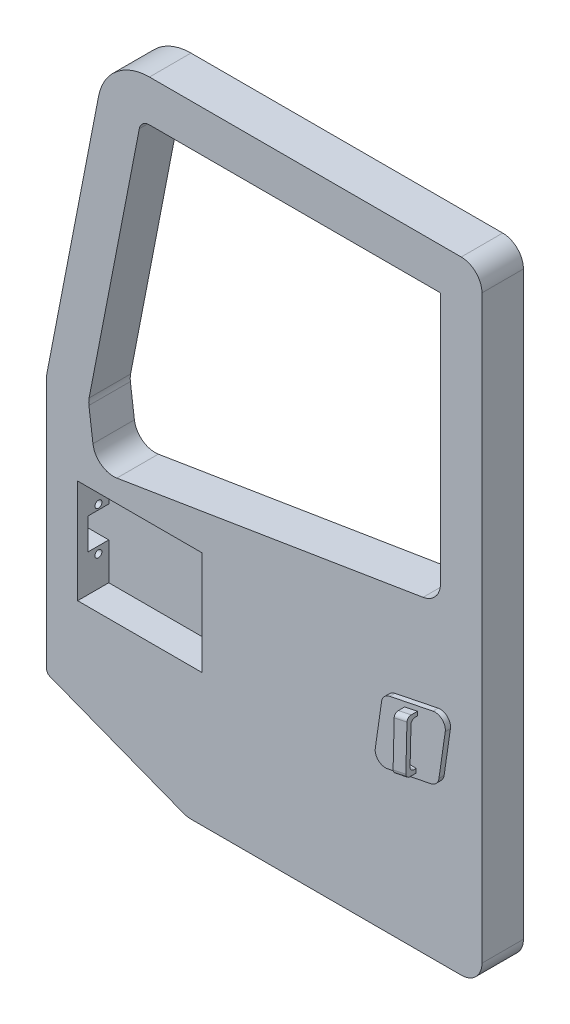
SolidWorks part; units mm, degrees
ref_plane "Front Plane" through (0, 0, 0) normal (0, 0, 1) x (1, 0, 0)
ref_plane "Top Plane" through (0, 0, 0) normal (0, 1, 0) x (1, 0, 0)
ref_plane "Right Plane" through (0, 0, 0) normal (1, 0, 0) x (0, 0, -1)
sketch "Sketch2" plane through (0, 0, 0) normal (0, 0, 1) x (1, 0, 0)
  line L0 (-405.8971, 659.2079) -> (-532.5433, 7.5919)
  line L1 (-179.7693, -762.022) -> (482.6, -762.022)
  line L3 (-281.2299, 761.978) -> (482.6, 761.978)
  line L4 (533.4, -711.222) -> (533.4, 711.178)
  line L5 (-459.8603, -656.939) -> (-452.0517, -645.784) construction
  line L6 (-417.9715, 597.0829) -> (44.1715, -63.1001) construction
  line L8 (-525.2852, -631.9868) -> (-198.1028, -758.5984)
  line L9 (-306.1633, 639.824) -> (-429.1581, 6.9955)
  line L10 (-429.6693, -9.2299) -> (-419.7789, -85.4932)
  line L14 (-281.2299, 660.378) -> (431.8, 660.378)
  line L15 (389.1621, -6.9365) -> (-361.2381, -129.0997)
  line L16 (431.7995, 43.2033) -> (431.8, 660.378)
  line L17 (431.8, -660.422) -> (431.8, 660.378) construction
  line L18 (-170.2829, -660.422) -> (431.8, -660.422) construction
  line L20 (-354.461, -589.1496) -> (-170.2829, -660.422) construction
  line L21 (-55.5325, -79.3316) -> (521.0599, 744.3665) construction
  line L22 (-306.1633, 639.824) -> (-430.7268, -1.0758) construction
  line L23 (-430.7268, -1.0758) -> (-354.461, -589.1496) construction
  line L24 (-416.9351, -673.9156) -> (-198.1028, -758.5984) construction
  line L25 (-179.7693, -762.022) -> (482.6, -762.022)
  line L27 (-281.2299, 761.978) -> (482.6, 761.978)
  line L28 (533.4, -711.222) -> (533.4, 711.178)
  line L29 (-459.8603, -656.939) -> (521.0599, 744.3665) construction
  line L30 (-417.9715, 597.0829) -> (521.0843, -744.3822) construction
  line L31 (-533.4018, 0.6529) -> (-448.7537, -652.0554) construction
  line L34 (-281.2299, 761.978) -> (482.6, 761.978)
  line L35 (-533.4018, 0.6529) -> (-533.4018, -620.1427)
  line L36 (-179.7693, -762.022) -> (482.6, -762.022)
  line L37 (533.4, 711.178) -> (533.4, -711.222)
  line L38 (-417.9715, 597.0829) -> (521.0843, -744.3822) construction
  line L39 (-460.0617, -657.2267) -> (521.0599, 744.3665) construction
  arc A0 (-405.8971, 659.2079) -> (-281.2299, 761.978) centre (-281.2299, 634.978) cw
  arc A2 (-532.5433, 7.5919) -> (-533.4018, 0.6529) centre (-482.6765, -2.1001) ccw
  arc A3 (533.4, 711.178) -> (482.6, 761.978) centre (482.6, 711.178) ccw
  arc A4 (482.6, -762.022) -> (533.4, -711.222) centre (482.6, -711.222) ccw
  arc A5 (-198.1028, -758.5984) -> (-179.7693, -762.022) centre (-179.7693, -711.222) ccw
  arc A7 (-354.461, -589.1496) -> (-354.461, -589.1496) centre (-354.461, -589.1496) ccw
  arc A8 (-170.2829, -660.422) -> (-170.2829, -660.422) centre (-170.2829, -660.422) ccw
  arc A9 (431.8, -660.422) -> (431.8, -660.422) centre (431.8, -660.422) ccw
  arc A10 (431.8, 660.378) -> (431.8, 660.378) centre (431.8, 660.378) ccw
  arc A11 (-306.1633, 639.824) -> (-281.2299, 660.378) centre (-281.2299, 634.978) cw
  arc A12 (-429.1581, 6.9955) -> (-429.6693, -9.2299) centre (-379.2912, -2.6964) ccw
  arc A13 (-430.7268, -1.0758) -> (-430.7268, -1.0758) centre (-430.7268, -1.0758) ccw construction
  arc A14 (431.7995, 43.2033) -> (389.1621, -6.9365) centre (380.9995, 43.2034) cw
  arc A15 (-419.7789, -85.4932) -> (-361.2381, -129.0997) centre (-369.4008, -78.9598) ccw
  arc A16 (-448.7537, -652.0554) -> (-416.9351, -673.9156) centre (-390.71, -601.6569) ccw construction
  arc A17 (-533.4018, -620.1427) -> (-525.2852, -631.9868) centre (-520.7018, -620.1427) ccw
  point P0 (0, 0)
  point P16 (-533.4, -0.0244)
  point P56 (0, 0)
  point P61 (0, 0)
  dimension "D3" = 127
  dimension "D5" = 50.8
  dimension "D6" = 50.8
  dimension "D8" = 50.8
  dimension "D2" = 12.7
  dimension "D1" = 1066.8
  dimension "D4" = 1524
  dimension "D7" = 101.6
extrude "Boss-Extrude1" add sketch "Sketch2" along normal mid plane 101.6 contours L8 A5 L1 A4 L4 A3 L3 A0 L0 A2 A15 L10 A12 L9 A11 L14 L16 A14 L15 region at (29.3865, -188.1823, 0)
sketch "Sketch3" plane through (0, 0, 50.8) normal (0, 0, 1) x (1, 0, 0)
  line L0 (320.1959, -245.101) -> (425.9265, -223.6716)
  line L3 (314.9201, -401.6691) -> (420.6507, -380.2397)
  line L4 (456.113, -252.1835) -> (440.7462, -358.9639)
  line L5 (300.1004, -266.3768) -> (284.7336, -373.1572)
  line L6 (310.4001, -194.8067) -> (287.3499, -354.9772) construction
  line L7 (-487.6326, -408.8312) -> (533.4008, -201.8888) construction
  line L8 (-457.3598, -558.1943) -> (563.6737, -351.2518) construction
  line L9 (461.2461, -216.515) -> (438.1959, -376.6855) construction
  line L10 (373.0612, -234.3863) -> (367.7854, -390.9544) construction
  line L11 (360.2667, -236.9795) -> (354.9908, -393.5476)
  line L12 (385.8558, -231.7931) -> (380.58, -388.3612)
  line L13 (360.3684, -233.9586) -> (355.0926, -390.5267) construction
  line L14 (385.754, -234.814) -> (380.4782, -391.3821) construction
  arc A0 (300.1004, -266.3768) -> (320.1959, -245.101) centre (325.2414, -269.9949) cw
  arc A1 (284.7336, -373.1572) -> (314.9201, -401.6691) centre (309.8746, -376.7752) ccw
  arc A2 (440.7462, -358.9639) -> (420.6507, -380.2397) centre (415.6052, -355.3458) cw
  arc A3 (456.113, -252.1835) -> (425.9265, -223.6716) centre (430.972, -248.5655) ccw
  dimension "D3" = 25.4
  dimension "D1" = 152.4
  dimension "D2" = 152.4
  dimension "D4" = 12.7
  dimension "D5" = 12.7
extrude "Boss-Extrude2" add sketch "Sketch3" along normal blind 12.7 contours L5 A1 L3 L11 L0 A0 | L4 A3 L0 L12 L3 A2 | L12 L0 L11 L3 region at (325.2101, -323.7797, 50.8) region at (370.4233, -312.6704, 50.8) region at (415.6365, -301.561, 50.8)
sketch "Sketch5" plane through (0, 0, 50.8) normal (0, 0, 1) x (1, 0, 0)
  line L0 (-429.6693, -9.2299) -> (-419.7789, -85.4932) construction
  line L1 (389.1621, -6.9365) -> (-361.2381, -129.0997) construction
  line L2 (431.7995, 43.2033) -> (431.8, 660.378) construction
  line L3 (-281.2299, 660.378) -> (431.8, 660.378) construction
  line L4 (-306.1633, 639.824) -> (-429.1581, 6.9955) construction
  line L5 (-429.6693, -9.2299) -> (-419.7789, -85.4932)
  line L6 (-179.7693, -762.022) -> (482.6, -762.022)
  line L12 (-179.7693, -762.022) -> (482.6, -762.022)
  line L18 (389.1621, -6.9365) -> (-361.2381, -129.0997)
  line L19 (431.7995, 43.2033) -> (431.8, 660.378)
  line L20 (-281.2299, 660.378) -> (431.8, 660.378)
  line L21 (-306.1633, 639.824) -> (-429.1581, 6.9955)
  line L28 (387.9598, -243.0291) -> (384.7172, -375.8602)
  line L29 (353.4927, -382.1888) -> (356.7353, -249.3577)
  line L30 (387.9598, -243.0291) -> (356.7353, -249.3577)
  line L31 (384.7172, -375.8602) -> (353.4927, -382.1888)
  line L32 (320.1959, -245.101) -> (425.9265, -223.6716) construction
  line L33 (314.9201, -401.6691) -> (420.6507, -380.2397) construction
  line L34 (320.1959, -245.101) -> (425.9265, -223.6716) construction
  line L35 (314.9201, -401.6691) -> (420.6507, -380.2397) construction
  arc A0 (-419.7789, -85.4932) -> (-361.2381, -129.0997) centre (-369.4008, -78.9598) ccw construction
  arc A1 (389.1621, -6.9365) -> (431.7995, 43.2033) centre (380.9995, 43.2034) ccw construction
  arc A2 (-281.2299, 660.378) -> (-306.1633, 639.824) centre (-281.2299, 634.978) ccw construction
  arc A3 (-429.1581, 6.9955) -> (-429.6693, -9.2299) centre (-379.2912, -2.6964) ccw construction
  arc A4 (-419.7789, -85.4932) -> (-361.2381, -129.0997) centre (-369.4008, -78.9598) ccw
  arc A5 (389.1621, -6.9365) -> (431.7995, 43.2033) centre (380.9995, 43.2034) ccw
  arc A18 (-281.2299, 660.378) -> (-306.1633, 639.824) centre (-281.2299, 634.978) ccw
  arc A19 (-429.1581, 6.9955) -> (-429.6693, -9.2299) centre (-379.2912, -2.6964) ccw
  dimension "D2" = 11.43
  dimension "D3" = 11.43
  dimension "D1" = 0
extrude "Boss-Extrude4" add sketch "Sketch5" along normal blind 38.1 contours L31 L28 L30 L29 region at (370.7262, -312.609, 50.8)
sketch "Sketch6" plane through (393.6581, -9.61, 0) normal (0.9997, -0.0244, 0) x (0, 0, -1)
  line L9 (-63.5, -356.1994) -> (-78.74, -356.1994)
  line L10 (-78.74, -356.1994) -> (-78.74, -243.6487)
  line L11 (-78.74, -243.6487) -> (-63.5, -243.6487)
  line L12 (-63.5, -356.1994) -> (-78.74, -356.1994)
  line L13 (-78.74, -356.1994) -> (-78.74, -243.6487)
  line L14 (-78.74, -243.6487) -> (-63.5, -243.6487)
  line M5 (-63.5, -366.3594) -> (-63.5, -233.4887)
  dimension "D1" = 10.16
extrude "Cut-Extrude6" cut sketch "Sketch6" against normal through all and the other way through all contours L14 L13 L12 M5 region at (386.3385, -309.4447, 71.12)
fillet "Fillet5" radius 10.16 4 edges at (369.1049, -379.0245, 88.9) (369.4394, -365.3242, 78.74) (372.1861, -252.8071, 78.74) (372.3476, -246.1934, 88.9)
sketch "Sketch7" plane through (-533.4018, 59.3738, 0) normal (1, 0, 0) x (0, 0, 1)
  line L0 (0, 821.3958) -> (0, -702.6042) construction
  line L1 (50.8, 821.3958) -> (-50.8, 821.3958) construction
  line L2 (50.8, -702.6042) -> (-50.8, -702.6042) construction
  line L3 (50.8, 58.7209) -> (-50.8, 58.7209) construction
  line L4 (-31.75, 84.1209) -> (31.75, 84.1209)
  line L5 (-31.75, 84.1209) -> (-31.75, 236.5209)
  line L6 (-31.75, 236.5209) -> (31.75, 236.5209)
  line L11 (31.75, 84.1209) -> (31.75, 236.5209)
  line L12 (-31.75, 84.1209) -> (31.75, 236.5209) construction
  line L13 (-31.75, 236.5209) -> (31.75, 84.1209) construction
  line L21 (-31.75, 642.9209) -> (31.75, 642.9209)
  line L28 (-31.75, 642.9209) -> (-31.75, 490.5209)
  line L29 (-31.75, 490.5209) -> (31.75, 490.5209)
  line L30 (31.75, 642.9209) -> (31.75, 490.5209)
  line L31 (-31.75, 642.9209) -> (31.75, 490.5209) construction
  line L32 (-31.75, 490.5209) -> (31.75, 642.9209) construction
  point P6 (0, 160.3209)
  point P13 (0, 566.7209)
  dimension "D1" = 63.5
  dimension "D2" = 152.4
  dimension "D3" = 25.4
  dimension "D4" = 254
extrude "Boss-Extrude5" add sketch "Sketch7" against normal blind 12.7
sketch "Sketch13" plane through (-546.1018, 0, 0) normal (-1, 0, 0) x (0, 0, 1)
  line L0 (0, -24.7471) -> (0, -177.1471) construction
  line L3 (-31.75, -24.7471) -> (31.75, -24.7471) construction
  line L6 (31.75, -177.1471) -> (-31.75, -177.1471) construction
  line L9 (31.75, -100.9471) -> (-31.75, -100.9471) construction
  line L10 (31.75, -24.7471) -> (31.75, -177.1471) construction
  line L11 (-31.75, -177.1471) -> (-31.75, -24.7471) construction
  line L12 (0, -431.1471) -> (0, -583.5471) construction
  line L13 (-31.75, -431.1471) -> (31.75, -431.1471) construction
  line L14 (31.75, -583.5471) -> (-31.75, -583.5471) construction
  line L15 (31.75, -507.3471) -> (-31.75, -507.3471) construction
  line L16 (31.75, -431.1471) -> (31.75, -583.5471) construction
  line L17 (-31.75, -583.5471) -> (-31.75, -431.1471) construction
  circle A4 centre (0, -50.1471) radius 11.43
  circle A6 centre (0, -151.7471) radius 11.43
  circle A7 centre (0, -456.5471) radius 11.43
  circle A8 centre (0, -558.1471) radius 11.43
  dimension "D1" = 50.8
  dimension "D2" = 22.86
  dimension "D3" = 50.8
  dimension "D4" = 22.86
extrude "Cut-Extrude7" cut sketch "Sketch13" against normal blind 46.99
sketch "Sketch14" plane through (-533.4018, 0, 0) normal (-1, 0, 0) x (0, 0, 1)
  line L0 (0, 761.978) -> (0, -758.5984) construction
  line L3 (50.8, 761.978) -> (-50.8, 761.978) construction
  line L4 (50.8, -758.5984) -> (-50.8, -758.5984) construction
  line L6 (-25.4, -346.3817) -> (25.4, -346.3817)
  line L7 (-25.4, -346.3817) -> (-25.4, -270.1817)
  line L8 (-25.4, -270.1817) -> (25.4, -270.1817)
  line L9 (25.4, -346.3817) -> (25.4, -270.1817)
  line L10 (-25.4, -346.3817) -> (25.4, -270.1817) construction
  line L11 (-25.4, -270.1817) -> (25.4, -346.3817) construction
  circle A0 centre (0, -257.9183) radius 8.5706
  circle A1 centre (0, -363.1476) radius 8.5706
  point P6 (0, -308.2817)
  dimension "D2" = 76.2
sketch "Sketch16" plane through (0, 0, 50.8) normal (0, 0, 1) x (1, 0, 0)
  line L1 (-457.2018, -183.3239) -> (-457.2018, -437.3239)
  line L3 (-152.4018, -437.3239) -> (-152.4018, -183.3239)
  line L5 (-533.4018, 0.6529) -> (-533.4018, -620.1427) construction
  line L6 (-457.2018, -183.3239) -> (-152.4018, -183.3239)
  line L7 (-457.2018, -437.3239) -> (-152.4018, -437.3239)
  point P4 (0, 0)
  point P5 (0, 0)
  dimension "D1" = 304.8
  dimension "D4" = 76.2
extrude "Cut-Extrude8" cut sketch "Sketch16" against normal blind 76.2
extrude "Cut-Extrude9" cut sketch "Sketch14" against normal up to surface (76.2 mm away) contours A0 | A1 | L7 L8 L9 L6 region at (-533.4018, -257.9183, 0) region at (-533.4018, -363.1476, 0) up to face at (-457.2018, -310.3239, 12.7)
equation "\"doorwidth\"= 42in"
equation "\"D1@Sketch2\"=\"doorwidth\""
equation "\"doorheight\"= 60in"
equation "\"D4@Sketch2\"=\"doorheight\""
equation "\"doorthickness\"= 4in"
equation "\"D1@Boss-Extrude1\"=\"doorthickness\""
equation "\"hingewidth\"= 2.5in"
equation "\"hingeheight\"= 6in"
equation "\"distanceofhinges\"= 10in"
equation "\"actuator slot width\"= 2in"
equation "\"actuator slot height\"= 3in"
equation "\"D2@Sketch14\"=\"actuator slot height\""
equation "\"D1@Sketch14\"=\"actuator slot width\""
equation "\"D1@Sketch7\"=\"hingewidth\""
equation "\"D2@Sketch7\"=\"hingeheight\""
equation "\"D4@Sketch7\"=\"distanceofhinges\""
